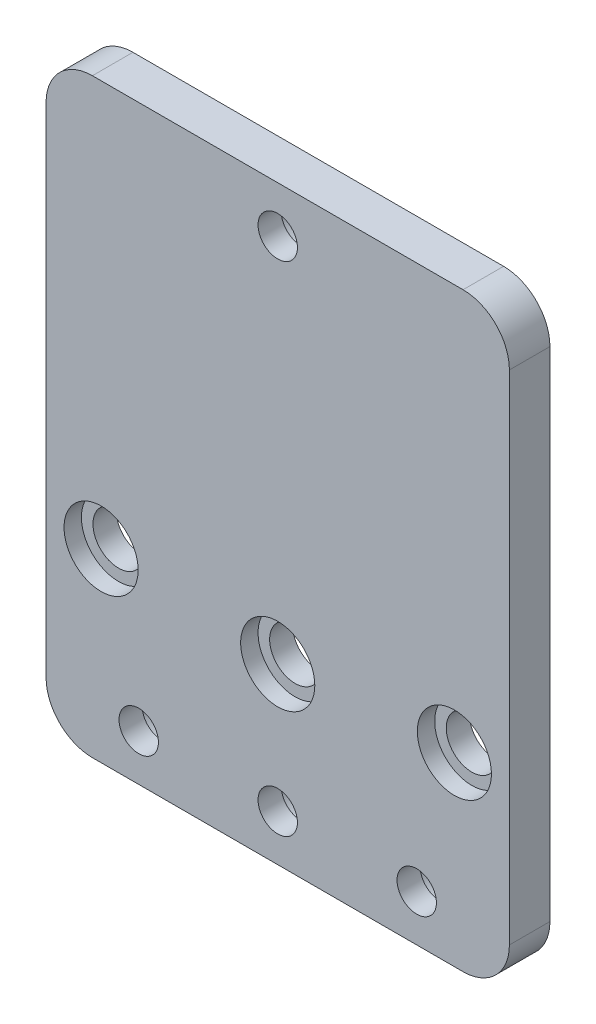
SolidWorks part; units mm, degrees
ref_plane "前视基准面" through (0, 0, 0) normal (0, 0, 1) x (1, 0, 0)
ref_plane "上视基准面" through (0, 0, 0) normal (0, 1, 0) x (1, 0, 0)
ref_plane "右视基准面" through (0, 0, 0) normal (1, 0, 0) x (0, 0, -1)
other "Configuration Table"
sketch "草图2" plane through (0, 0, 0) normal (0, 0, 1) x (1, 0, 0)
  line L1 (8220.9694, 3044.3541) -> (8252.9694, 3044.3541)
  line L2 (8216.9694, 3040.3541) -> (8216.9694, 2997.3663)
  line L3 (8220.9694, 2993.3663) -> (8252.9694, 2993.3663)
  line L4 (8256.9694, 3040.3541) -> (8256.9694, 2997.3663)
  circle A0 centre (8236.9694, 3040.3541) radius 1.7
  circle A1 centre (8248.9694, 2997.3663) radius 1.7
  circle A2 centre (8236.9694, 2997.3663) radius 1.7
  circle A3 centre (8224.9694, 2997.3663) radius 1.7
  circle A4 centre (8236.9694, 3008.3663) radius 2.2
  circle A5 centre (8221.7194, 3009.3663) radius 2.2
  circle A6 centre (8252.2194, 3009.3663) radius 2.2
  arc A7 (8252.9694, 2993.3663) -> (8256.9694, 2997.3663) centre (8252.9694, 2997.3663) ccw
  arc A8 (8216.9694, 2997.3663) -> (8220.9694, 2993.3663) centre (8220.9694, 2997.3663) ccw
  arc A9 (8220.9694, 3044.3541) -> (8216.9694, 3040.3541) centre (8220.9694, 3040.3541) ccw
  arc A10 (8252.9694, 3044.3541) -> (8256.9694, 3040.3541) centre (8252.9694, 3040.3541) cw
  point P18 (0, 0)
  point P19 (0, 0)
  point P30 (8221.7517, 3004.498)
  dimension "D8" = 30.5
  dimension "D10" = 4
  dimension "D11" = 4
  dimension "D1" = 42.9878
  dimension "D2" = 4
  dimension "D3" = 4
  dimension "D4" = 12
  dimension "D5" = 12
  dimension "D6" = 8
  dimension "D7" = 8
  dimension "D9" = 15
  dimension "D12" = 16
extrude "凸台-拉伸1" add sketch "草图2" along normal blind 3.5
sketch "草图3" plane through (0, 0, 0) normal (0, 0, -1) x (-1, 0, 0)
  circle A0 centre (-8236.9694, 3040.3541) radius 2.7
  circle A1 centre (-8248.9694, 2997.3663) radius 2.7
  circle A2 centre (-8236.9694, 2997.3663) radius 2.7
  circle A3 centre (-8224.9694, 2997.3663) radius 2.7
extrude "凸台-拉伸2" add sketch "草图3" against normal blind 1.5 separate body
sketch "草图4" plane through (0, 0, 3.5) normal (0, 0, 1) x (1, 0, 0)
  circle A0 centre (8236.9694, 3008.3663) radius 3.2
  circle A1 centre (8221.7194, 3009.3663) radius 3.2
  circle A2 centre (8252.2194, 3009.3663) radius 3.2
extrude "凸台-拉伸3" add sketch "草图4" against normal blind 1.5 separate body
combine bodies "组合1" operation type subtract main body 106 bodies to subtract 111 113 112 110 109 108 107
